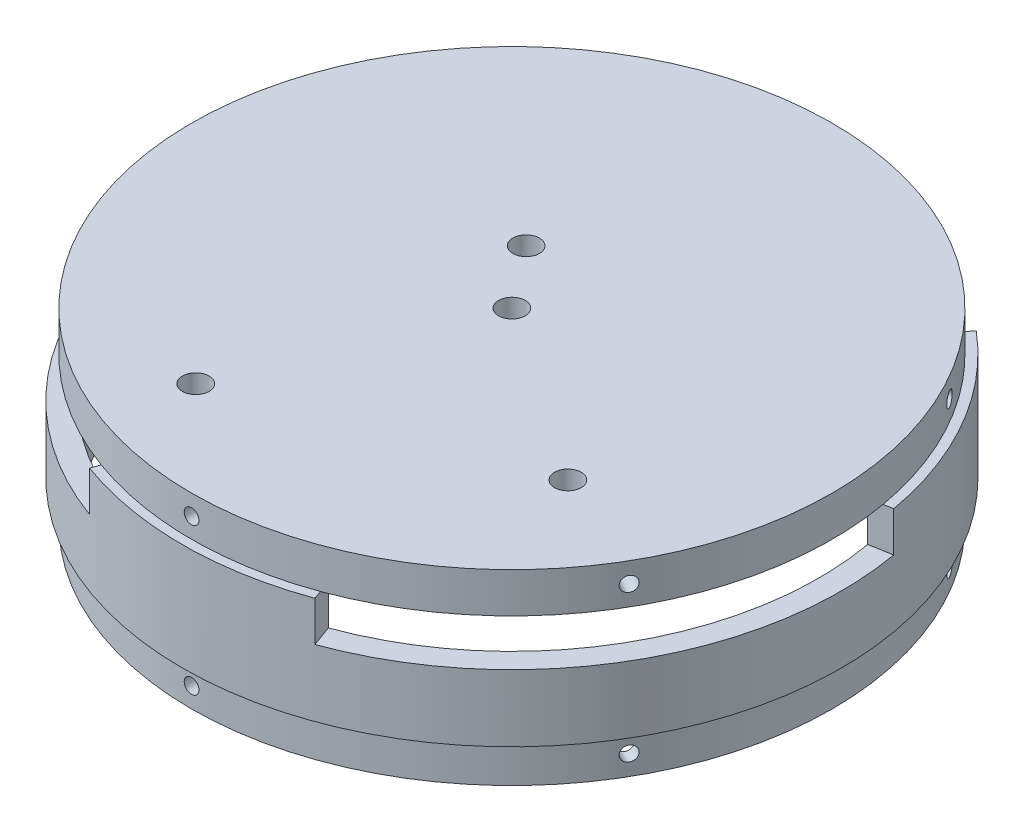
SolidWorks part; units mm, degrees
ref_plane "Front Plane" through (0, 0, 0) normal (0, 0, 1) x (1, 0, 0)
ref_plane "Top Plane" through (0, 0, 0) normal (0, 1, 0) x (1, 0, 0)
ref_plane "Right Plane" through (0, 0, 0) normal (1, 0, 0) x (0, 0, -1)
sketch "Sketch1" plane through (0, 0, 0) normal (0, 1, 0) x (1, 0, 0)
  line L0 (0, 0) -> (-50.3682, 60.0265)
  line L1 (0, 0) -> (50.3682, 60.0265)
  line L2 (0, 0) -> (0, 72.1431) construction
  circle A0 centre (0, 0) radius 78.359
  circle A1 centre (0, 0) radius 73.025
  circle A2 centre (0, 0) radius 76.1746
  dimension "D1" = 156.718
  dimension "D2" = 146.05
  dimension "D3" = 152.3492
  dimension "D4" = 80
extrude "Boss-Extrude1" add sketch "Sketch1" along normal blind 25.4 contours L2 A2 L1 A0 | L2 A1 L1 A2 | L2 A2 L1 A1 | L2 A0 L1 A2 | A2 L2 A1 L0 | A0 L2 A2 L0 | A2 L2 A0 L0 | A1 L2 A2 L0 region at (-31.7206, 0, 68.0251) region at (-47.1858, 0, -57.7895) region at (-33.0764, 0, 70.9325) region at (-48.8794, 0, -59.85)
ref_plane "Plane1" through (0, 12.7, 0) normal (0, 1, 0) x (1, 0, 0)
extrude "Boss-Extrude2" add sketch "Sketch1<3>" along normal blind 9.525 from surface contours A2 L2 A1 L0 | L2 A2 L1 A1 | L2 A1 L1 A2 | A1 L2 A2 L0 region at (-31.7206, 0, 68.0251) region at (-47.1858, 0, -57.7895) starting at face at (0, 25.4, 73.025)
sketch "Sketch1<3>" plane through (0, 0, 0) normal (0, 1, 0) x (1, 0, 0) same geometry as "Sketch1"
extrude "Boss-Extrude3" add sketch "Sketch1<4>" against normal blind 9.525 contours A2 L2 A1 L0 | A1 L2 A2 L0 | L2 A1 L1 A2 | L2 A2 L1 A1 region at (-31.7206, 0, 68.0251) region at (-47.1858, 0, -57.7895)
sketch "Sketch1<4>" plane through (0, 0, 0) normal (0, 1, 0) x (1, 0, 0) same geometry as "Sketch1"
ref_plane "Plane2" through (0, 0, -76.1746) normal (0, 0, -1) x (-1, 0, 0)
ref_plane "Plane5" through (0, 25.4, 0) normal (0, 1, 0) x (1, 0, 0)
ref_axis "Axis1" through (0, 0, 0) along (0, 1, 0)
sketch "Sketch3" plane through (0, 0, -76.1746) normal (0, 0, -1) x (-1, 0, 0)
  line L0 (76.1746, 0) -> (-76.1746, 0) construction
  line L1 (-76.1746, -9.525) -> (76.1746, -9.525) construction
  line L2 (76.1746, 25.4) -> (-76.1746, 25.4) construction
  line L3 (76.1746, 34.925) -> (-76.1746, 34.925) construction
  line L4 (76.1746, 0) -> (-76.1746, 0)
  line L5 (-76.1746, -9.525) -> (76.1746, -9.525)
  line L6 (76.1746, 25.4) -> (-76.1746, 25.4)
  line L7 (76.1746, 34.925) -> (-76.1746, 34.925)
  line L8 (0, 34.925) -> (0, 25.4)
  line L9 (0, 0) -> (0, -9.525)
  circle A0 centre (0, 30.1625) radius 1.75
  circle A1 centre (0, -4.7625) radius 1.75
  point P12 (0, 30.1625)
  point P13 (0, -4.7625)
  point P14 (-77.5445, 179.1871)
  dimension "D1" = 3.5
extrude "Cut-Extrude2" cut sketch "Sketch3" against normal blind 9.525 contours L8 A0 | L8 A0 | L9 A1 | L9 A1 region at (-0.7427, 30.1625, -76.1746) region at (0.7427, 30.1625, -76.1746) region at (-0.7427, -4.7625, -76.1746) region at (0.7427, -4.7625, -76.1746)
extrude "Cut-Extrude3" cut sketch "Sketch1<7>" against normal blind 9.525 from surface contours L2 A1 L1 A2 | A1 L2 A2 L0 | A2 L2 A0 L0 | L2 A2 L1 A0 region at (-47.1858, 0, -57.7895) region at (-48.8794, 0, -59.85) starting at plane "Plane5"
sketch "Sketch1<7>" plane through (0, 0, 0) normal (0, 1, 0) x (1, 0, 0) same geometry as "Sketch1"
pattern_circular "CirPattern2" count 3 over 360 about axis through (0, 0, 0) along (0, 1, 0) of "Cut-Extrude3"
ref_plane "Plane3" through (0, 34.925, 0) normal (0, 1, 0) x (1, 0, 0)
sketch "Sketch4" plane through (0, 34.925, 0) normal (0, 1, 0) x (1, 0, 0)
  circle A0 centre (0, 0) radius 73.025
  dimension "D1" = 146.05
extrude "Boss-Extrude4" add sketch "Sketch4" against normal blind 9.525
pattern_circular "CirPattern3" count 6 over 360 about axis through (0, 0, 0) along (0, 1, 0) of "Cut-Extrude2"
sketch "Sketch5" plane through (0, 34.925, 0) normal (0, 1, 0) x (1, 0, 0)
  line L0 (-15.0069, -36.2322) -> (-26.8004, -73.6334) construction
  line L1 (-15.0069, -36.2322) -> (-22.0157, -53.1519) construction
  circle A0 centre (0, 0) radius 3.175
  circle A1 centre (-22.0157, -53.1519) radius 3.175
  circle A2 centre (0, 0) radius 57.531 construction
  circle A3 centre (23.8745, -31.1125) radius 57.531 construction
  circle A4 centre (-11.1485, 14.5297) radius 3.175
  circle A5 centre (-15.0069, -36.2322) radius 57.531 construction
  circle A6 centre (42.0318, -28.7224) radius 3.175
  point P17 (2.9559, -22.4482)
  dimension "D1" = 6.35
  dimension "D3" = 6.35
  dimension "D2" = 57.531
  dimension "D5" = 5
extrude "Cut-Extrude4" cut sketch "Sketch5" against normal through all
equation "\"AB_Coupler_OD_Length\"= 1in"
equation "\"AB_Coupling_Section_Length\"= 0.375in"
equation "\"AB_Coupler_Length\"= \"AB_Coupler_OD_Length\" + \"AB_Coupling_Section_Length\" * 2"
equation "\"D1@Boss-Extrude2\"=\"AB_Coupling_Section_Length\""
equation "\"D1@Boss-Extrude3\"=\"AB_Coupling_Section_Length\""
equation "\"D1@Boss-Extrude1\" = \"AB_Coupler_OD_Length\""
equation "\"Cutout_Angle\" = 80"
equation "\"AB_Coupler_Num_Screws\"= 6"
equation "\"Num_Cutouts\" = 3"
equation "\"D4@Sketch1\"=\"Cutout_Angle\""
equation "\"D1@CirPattern2\"=\"Num_Cutouts\""
equation "\"D1@CirPattern3\"=\"AB_Coupler_Num_Screws\""
equation "\"AB_Coupler_OD\"= 6.17in"
equation "\"AB_Coupler_ID\"= 5.75in"
equation "\"AB_Coupler_Surface_Diameter\"= 5.998in"
equation "\"D3@Sketch1\"=\"AB_Coupler_Surface_Diameter\""
equation "\"D2@Sketch1\"=\"AB_Coupler_ID\""
equation "\"D1@Sketch1\"=\"AB_Coupler_OD\""
equation "\"AB_Coupling_Screw_Diameter\"= 0.1065in"
equation "\"Aft_Section_Length\"= 40in"
equation "\"Aft_Lower_Length\"= 22in"
equation "\"Aft_Upper_Length\"= \"Aft_Section_Length\" - \"Aft_Lower_Length\" - \"AB_Coupler_OD_Length\""
equation "\"Mid_Coupler_Length\" = 13in"
equation "\"Lead_Screw_Dist\" = 2.25in"
equation "\"Lead_Screw_Diam\" = (27/64)*1in"
equation "\"Lead_Screw_Length\" = (\"Mid_Coupler_Length\" + 2*0.375in + 2*0.5in)"
equation "\"Bodytube_OD\" = 6.17in"
equation "\"Paddle_Pin_Offset\" = .25in"
equation "\"Bodytube_ID\" = 5.998in"
equation "\"Paddle_Pin_Radius\" = 2.25in"
equation "\"D1@Sketch4\"=\"AB_Coupler_ID\""
equation "\"D2@Sketch5\"=2.265"
